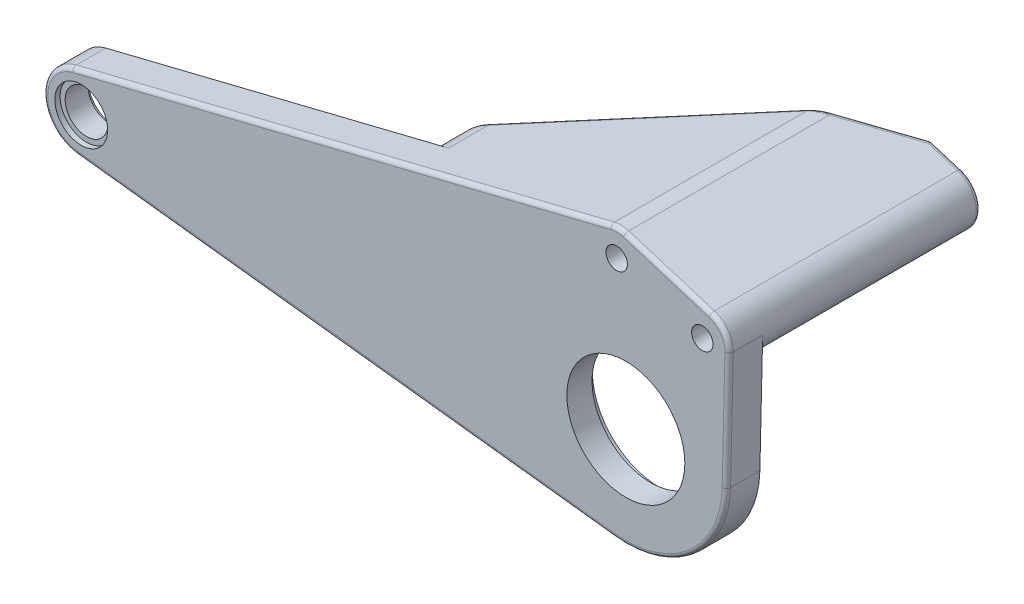
SolidWorks part; units mm, degrees
ref_plane "Front Plane" through (0, 0, 0) normal (0, 0, 1) x (1, 0, 0)
ref_plane "Top Plane" through (0, 0, 0) normal (0, 1, 0) x (1, 0, 0)
ref_plane "Right Plane" through (0, 0, 0) normal (1, 0, 0) x (0, 0, -1)
sketch "Sketch1" plane through (0, 0, 0) normal (0, 0, 1) x (1, 0, 0)
  line L0 (-1.7143, 6.935) -> (101.6, 32.4732)
  line L1 (101.6, 32.4732) -> (122.8448, 25.8964)
  line L2 (-0.8243, -7.096) -> (100.9894, -18.9228)
  line L4 (122.2324, -0.4428) -> (122.8448, 25.8964)
  line L5 (103.1875, 0) -> (122.8448, 25.8964) construction
  line L6 (103.1875, 0) -> (101.6, 32.4732) construction
  circle A0 centre (0, 0) radius 2.032
  arc A1 (-1.7143, 6.935) -> (-0.8243, -7.096) centre (0, 0) ccw
  arc A2 (100.9894, -18.9228) -> (122.2324, -0.4428) centre (103.1875, 0) ccw
  circle A3 centre (103.1875, 0) radius 11.176
  dimension "D1" = 4.064
  dimension "D2" = 7.1437
  dimension "D3" = 22.352
  dimension "D4" = 19.05
  dimension "D5" = 103.1875
  dimension "D6" = 40
  dimension "D7" = 32.512
  dimension "D8" = 1.5875
extrude "Boss-Extrude1" add sketch "Sketch1" along normal blind 6.35
fillet "Fillet1" radius 5.08 2 edges at (122.8448, 25.8964, 3.175) (101.6, 32.4732, 3.175)
sketch "Sketch5" plane through (0, 0, 0) normal (0, 0, -1) x (-1, 0, 0)
  circle A0 centre (-117.677, 22.1783) radius 2.032
  arc A2 (-119.1793, 27.0311) -> (-122.7556, 22.0602) centre (-117.677, 22.1783) ccw construction
  circle A4 centre (-101.4474, 27.2026) radius 2.032
  dimension "D1" = 4.064
extrude "Cut-Extrude2" cut sketch "Sketch5" against normal through all both and the other way through all
sketch "Sketch6" plane through (0, 0, 6.35) normal (0, 0, 1) x (1, 0, 0)
  circle A0 centre (0, 0) radius 4.05
  dimension "D1" = 8.1
extrude "Cut-Extrude3" cut sketch "Sketch6" against normal through all
sketch "Sketch7" plane through (0, 0, 6.35) normal (0, 0, 1) x (1, 0, 0)
  circle A0 centre (0, 0) radius 5
  dimension "D1" = 10
extrude "Cut-Extrude4" cut sketch "Sketch7" against normal blind 1
sketch "Sketch8" plane through (0, 0, 0) normal (0, 0, -1) x (-1, 0, 0)
  circle A0 centre (0, 0) radius 5.05
  dimension "D1" = 10.1
extrude "Cut-Extrude5" cut sketch "Sketch8" against normal blind 1
fillet "Fillet3" [suppressed] radius 0.7937
sketch "Sketch10" plane through (0, 0, 0) normal (0, 0, -1) x (-1, 0, 0)
  line L0 (-100.2284, 32.1342) -> (1.7143, 6.935) construction
  line L1 (-119.1793, 27.0311) -> (-102.9497, 32.0554) construction
  line L2 (-100.2284, 32.1342) -> (-63.2416, 22.9914)
  line L3 (-119.1793, 27.0311) -> (-102.9497, 32.0554)
  line L4 (-103.1875, 0) -> (-117.677, 22.1783) construction
  line L5 (-117.677, 22.1783) -> (-101.4474, 27.2026) construction
  line L6 (-65.7597, 12.8046) -> (-63.2416, 22.9914) construction
  line L7 (-98.0493, 20.7863) -> (-65.7597, 12.8046)
  line L9 (-121.5631, 22.1783) -> (-119.62, 18.8128)
  line L10 (-119.62, 18.8128) -> (-115.7339, 18.8128)
  line L11 (-115.7339, 18.8128) -> (-113.7908, 22.1783)
  line L12 (-113.7908, 22.1783) -> (-115.7339, 25.5438)
  line L13 (-115.7339, 25.5438) -> (-119.62, 25.5438)
  line L14 (-119.62, 25.5438) -> (-121.5631, 22.1783)
  line L15 (-105.3336, 27.2026) -> (-103.3905, 23.8371)
  line L16 (-103.3905, 23.8371) -> (-99.5043, 23.8371)
  line L17 (-99.5043, 23.8371) -> (-97.5613, 27.2026)
  line L18 (-97.5613, 27.2026) -> (-99.5043, 30.5681)
  line L19 (-99.5043, 30.5681) -> (-103.3905, 30.5681)
  line L20 (-103.3905, 30.5681) -> (-105.3336, 27.2026)
  arc A0 (-100.2284, 32.1342) -> (-102.9497, 32.0554) centre (-101.4474, 27.2026) ccw construction
  arc A1 (-119.1793, 27.0311) -> (-122.7556, 22.0602) centre (-117.677, 22.1783) ccw construction
  arc A2 (-100.2284, 32.1342) -> (-102.9497, 32.0554) centre (-101.4474, 27.2026) ccw
  arc A3 (-119.1793, 27.0311) -> (-122.7556, 22.0602) centre (-117.677, 22.1783) ccw
  arc A4 (-122.7556, 22.0602) -> (-114.8985, 17.9255) centre (-117.677, 22.1783) ccw
  arc A5 (-114.8985, 17.9255) -> (-98.0493, 20.7863) centre (-103.1875, 0) cw
  arc A6 (-63.2416, 22.9914) -> (-65.7597, 12.8046) centre (-64.5007, 17.898) cw
  circle A7 centre (-117.677, 22.1783) radius 3.3655 construction
  circle A8 centre (-101.4474, 27.2026) radius 3.3655 construction
  dimension "D2" = 6.731
  dimension "D1" = 38.1
extrude "Boss-Extrude3" add sketch "Sketch10" along normal blind 41.275
sketch "Sketch11" plane through (18.0592, 58.3354, 0) normal (0.2957, 0.9553, 0) x (0.9553, -0.2957, 0)
  line L0 (99.8222, 41.275) -> (51.076, 6.35)
  line L1 (51.076, 41.275) -> (51.076, 0) construction
  line L2 (53.6137, 0) -> (-3.6885, 0) construction
  line L3 (51.076, 6.35) -> (51.076, 41.275)
  line L4 (51.076, 41.275) -> (99.8222, 41.275)
  line L5 (110.9347, 0) -> (110.9347, 41.275) construction
  dimension "D1" = 6.35
  dimension "D2" = 11.1125
extrude "Cut-Extrude6" cut sketch "Sketch11" against normal through all
sketch "Sketch12" plane through (0, 0, 6.35) normal (0, 0, 1) x (1, 0, 0)
  line L0 (93.4998, 19.6617) -> (90.9817, 29.8485) construction
  line L1 (65.7597, 12.8046) -> (98.0493, 20.7863) construction
  line L2 (100.2284, 32.1342) -> (63.2416, 22.9914) construction
  circle A0 centre (64.5007, 17.898) radius 2.032
  circle A1 centre (92.2407, 24.7551) radius 2.032
  dimension "D1" = 4.064
  dimension "D2" = 28.575
extrude "Cut-Extrude7" [suppressed] cut sketch "Sketch12" against normal through all
ref_plane "Plane1" through (0, 0, 3.175) normal (0, 0, 1) x (1, 0, 0)
fillet "Fillet4" radius 0.7937 8 edges at (101.5944, 32.2805, 6.35) (111.0645, 29.5432, 6.35) (121.8006, 25.1451, 6.35) (122.494, 10.8087, 6.35) (115.6907, -14.3726, 6.35) (50.0826, -13.0094, 6.35) (-7.1294, -0.4522, 6.35) (49.2571, 19.5346, 6.35)
fillet "Fillet5" radius 0.7937 10 edges at (104.4319, 21.3757, -36.702) (81.9045, 16.7955, -22.2542) (59.4073, 16.639, -6.8898) (81.735, 27.5628, -19.8568) (101.5944, 32.2805, -32.4494) (112.8593, 19.1031, -41.275) (122.2743, 20.017, -41.275) (112.0598, 24.4324, -41.275) (108.1831, 30.4352, -37.3499) (116.2979, 27.9231, -41.275)
sketch "Sketch13" plane through (0, 0, 0) normal (0, 0, -1) x (-1, 0, 0)
  circle A0 centre (-103.1875, 0) radius 12.7
  dimension "D1" = 25.4
extrude "Cut-Extrude8" cut sketch "Sketch13" against normal blind 1.5875
mirror "Mirror1" [suppressed] of bodies 116 112 111
delete or keep bodies "Body-Delete/Keep 1" [suppressed] type delete bodies bodies 116
